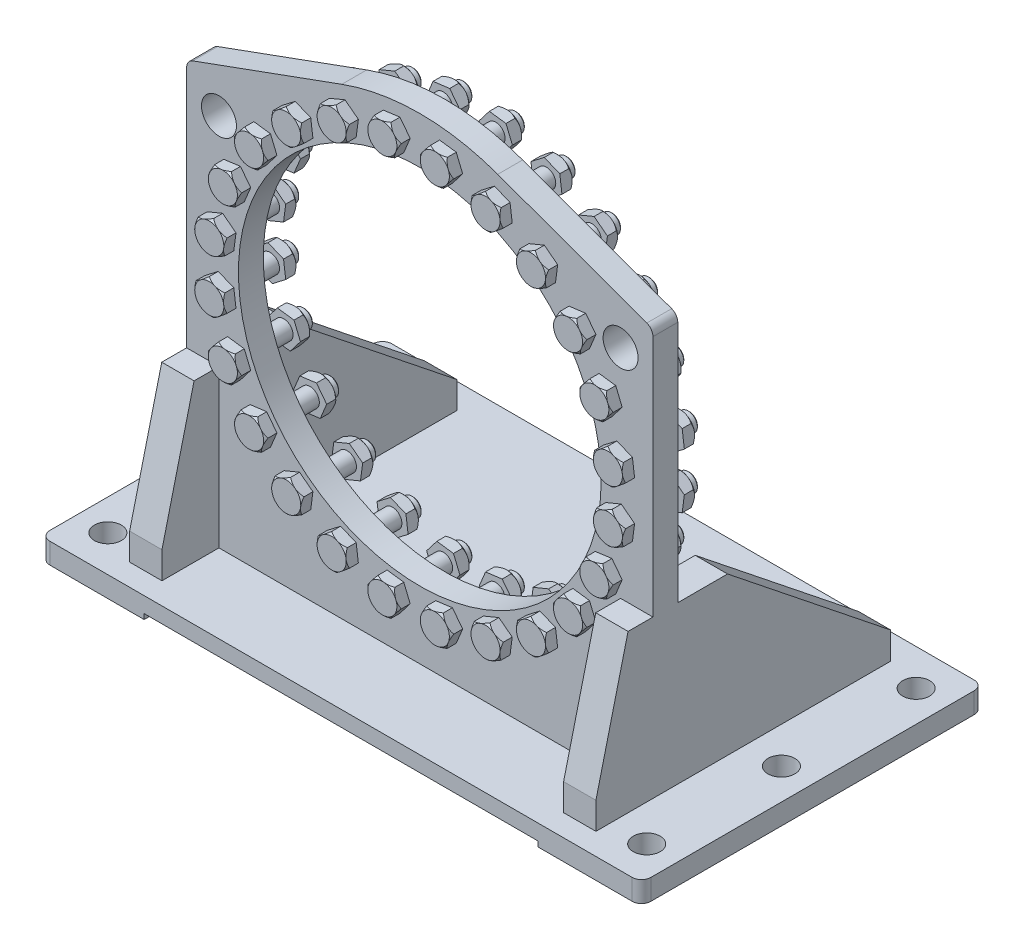
SolidWorks part; units mm, degrees
ref_plane "前视基准面" through (0, 0, 0) normal (0, 0, 1) x (1, 0, 0)
ref_plane "上视基准面" through (0, 0, 0) normal (0, 1, 0) x (1, 0, 0)
ref_plane "右视基准面" through (0, 0, 0) normal (1, 0, 0) x (0, 0, -1)
sketch "草图1" plane through (0, 0, 0) normal (1, 0, 0) x (0, 0, -1)
  line L1 (-305, 0) -> (24, 0) construction
  line L2 (0, 214) -> (24, 214)
  line L3 (24, 214) -> (24, 0)
  line L5 (0, 214) -> (0, 175)
  line L6 (0, 175) -> (-24, 175)
  line L10 (0, 194) -> (24, 194) construction
  line L32 (-24, 220) -> (-24, 175)
  line L34 (-48, -88.4) -> (48, -88.4)
  line L35 (48, -88.4) -> (205.5, -214)
  line L51 (205.5, -214) -> (205.5, -240)
  line L55 (205.5, -240) -> (-79, -240)
  line L56 (-79, -240) -> (-79, -214)
  line L57 (-79, -214) -> (-48, -88.4)
  line L58 (0, 175) -> (0, -260) construction
  line L59 (230, -260) -> (-100, -260)
  line L60 (455, -260) -> (325, -260) construction
  line L61 (325, -260) -> (195, -260) construction
  line L62 (24, 194) -> (34.8, 194) construction
  line L63 (195, -260) -> (65, -260) construction
  line L64 (65, -260) -> (-65, -260) construction
  line L65 (-24, 194) -> (-34.8, 194) construction
  line L66 (-24, 220) -> (0, 220)
  point P4 (24, 194)
  point P15 (0, 203)
  point P30 (43.8, 194)
  point P47 (-95, 0)
  point P48 (0, -88.4)
  point P52 (29.4, 194)
  point P53 (452, -260)
  dimension "D1" = 10.8
  dimension "G2" = 95
  dimension "C" = 24
  dimension "da" = 428
  dimension "d4" = 350
  dimension "k" = 388
  dimension "D2" = 21
  dimension "D3" = 24.5
  dimension "s" = 18
  dimension "D5" = 26
  dimension "D7" = 96
  dimension "D8" = 19.8
  dimension "n" = 24
  dimension "(c)" = 20
  dimension "(h)" = 260
  dimension "b" = 330
  dimension "m3" = 130
  dimension "(n)" = 35
  dimension "l2" = 210
  dimension "m4" = 240
  dimension "D6" = 171.6
  dimension "s(n)" = 3
  dimension "H" = 480
sketch "草图2" plane through (0, 0, 0) normal (0, 0, 1) x (1, 0, 0)
  line L0 (-190, -255) -> (190, -255)
  line L1 (190, -255) -> (190, -260)
  line L2 (290, -260) -> (-290, -260)
  line L3 (0, -260) -> (0, 0) construction
  line L5 (75.2444, 206.7324) -> (225, 152.2258)
  line L6 (225, 152.2258) -> (225, -260)
  line L7 (225, 121.0258) -> (193.8, 121.0258)
  line L8 (193.8, 121.0258) -> (193.8, 152.2258)
  line L9 (-260, -260) -> (-260, -240) construction
  line L10 (-260, -240) -> (225, -240)
  line L11 (193.8, -240) -> (193.8, -120)
  line L12 (193.8, -120) -> (225, -120)
  circle A0 centre (0, 0) radius 220
  circle A1 centre (193.8, 121.0258) radius 16.9
  circle A2 centre (0, 0) radius 175
  point P7 (0, -255)
  point P12 (0, 220)
  point P25 (-247, -260)
  dimension "D4" = 33.8
  dimension "D1" = 5
  dimension "e" = 380
  dimension "D2" = 70
  dimension "a" = 580
  dimension "d" = 450
  dimension "D3" = 120
  dimension "m1" = 520
  dimension "(s)" = 26
  dimension "D5" = 31.2
sketch "草图4" plane through (0, 0, 0) normal (0, 0, 1) x (1, 0, 0)
  line L0 (75.2444, 206.7324) -> (225, 152.2258) construction
  line L1 (225, 152.2258) -> (225, -260) construction
  line L2 (-260, -240) -> (225, -240) construction
  line L3 (75.2444, 206.7324) -> (225, 152.2258)
  line L4 (225, 152.2258) -> (225, -240)
  line L5 (-225, -240) -> (225, -240)
  line L6 (0, 214) -> (0, -240) construction
  line L7 (-225, 152.2258) -> (-225, -240)
  line L8 (-75.2444, 206.7324) -> (-225, 152.2258)
  circle A0 centre (0, 0) radius 220 construction
  circle A1 centre (193.8, 121.0258) radius 16.9 construction
  arc A2 (75.2444, 206.7324) -> (-75.2444, 206.7324) centre (0, 0) ccw
  circle A3 centre (193.8, 121.0258) radius 16.9
  circle A4 centre (-193.8, 121.0258) radius 16.9
  circle A5 centre (0, 0) radius 175 construction
  circle A6 centre (0, 0) radius 175
extrude "凸台-拉伸1" add sketch "草图4" along normal up to vertex (24 mm away) up to point (0, 220, 24)
sketch "草图6" plane through (0, 0, 0) normal (0, 0, -1) x (-1, 0, 0)
  line L0 (-26.4968, 201.2633) -> (-24.1473, 183.4173) construction
  line L1 (0, 175) -> (0, -260) construction
  circle A0 centre (0, 0) radius 194 construction
  circle A1 centre (-25.3221, 192.3403) radius 9
  circle A2 centre (0, 194) radius 9 construction
  dimension "D1" = 7.5
extrude "凸台-拉伸2" add sketch "草图6" along normal up to vertex (43.8 mm away) up to point (0, 194, -43.8)
chamfer "倒角1" distance 1.26 angle 45 1 edges at (16.3221, 192.3403, -43.8)
sketch "草图7" plane through (0, 0, 0) normal (0, 0, 1) x (1, 0, 0)
  line L0 (26.4968, 201.2633) -> (24.1473, 183.4173) construction
  line L1 (9.2488, 194.4564) -> (15.4528, 179.4785)
  line L2 (15.4528, 179.4785) -> (31.5261, 177.3624)
  line L3 (31.5261, 177.3624) -> (41.3954, 190.2242)
  line L4 (41.3954, 190.2242) -> (35.1913, 205.2021)
  line L5 (35.1913, 205.2021) -> (19.118, 207.3182)
  line L6 (19.118, 207.3182) -> (9.2488, 194.4564)
  circle A0 centre (25.3221, 192.3403) radius 14.04 construction
  dimension "D1" = 28.08
extrude "凸台-拉伸3" add sketch "草图7" against normal up to vertex (34.8 mm away) from vertex up to point (0, 194, -34.8) starting at point (0, 194, -24)
sketch "草图8" plane through (0, 0, -34.8) normal (0, 0, -1) x (-1, 0, 0)
  circle A0 centre (-25.3221, 192.3403) radius 14.04 construction
  circle A1 centre (-25.3221, 192.3403) radius 14.04
  circle A2 centre (-25.3221, 192.3403) radius 19.44
  dimension "D1" = 5.4
extrude "切除-拉伸1" cut sketch "草图8" against normal up to vertex (5.4 mm away) draft 45 up to point (0, 194, -29.4)
mirror "镜向2" about plane through (0, 0, 0) normal (0, 0, 1) of "切除-拉伸1", "凸台-拉伸3"
pattern_circular "阵列(圆周)1" count 24 over 360 about axis through (0, 0, 24) along (0, 0, -1) of "凸台-拉伸2", "倒角1", "凸台-拉伸3", "切除-拉伸1", "镜向2"
sketch "草图9" plane through (225, 0, 0) normal (-1, 0, 0) x (0, 0, 1)
  line L0 (-48, -88.4) -> (-205.5, -214) construction
  line L1 (48, -88.4) -> (-48, -88.4) construction
  line L2 (79, -214) -> (48, -88.4) construction
  line L3 (79, -240) -> (79, -214) construction
  line L12 (-205.5, -240) -> (79, -240) construction
  line L13 (-205.5, -214) -> (-205.5, -240) construction
  line L14 (-48, -88.4) -> (-205.5, -214)
  line L15 (48, -88.4) -> (-48, -88.4)
  line L16 (79, -214) -> (48, -88.4)
  line L17 (79, -240) -> (79, -214)
  line L18 (-205.5, -240) -> (79, -240)
  line L19 (-205.5, -214) -> (-205.5, -240)
extrude "凸台-拉伸4" add sketch "草图9" along normal up to vertex (31.2 mm away) up to point (193.8, -120, 0)
sketch "草图10" plane through (0, -240, 0) normal (0, -1, 0) x (1, 0, 0)
  line L1 (290, -230) -> (0, -230)
  line L2 (290, -230) -> (290, 100)
  line L3 (290, 100) -> (0, 100)
  line L4 (0, -230) -> (0, 100)
extrude "凸台-拉伸5" add sketch "草图10" along normal up to vertex (20 mm away) up to point (0, -260, -230)
sketch "草图11" plane through (0, -240, 0) normal (0, 1, 0) x (1, 0, 0)
  line L1 (0, 0) -> (0, -140.5) construction
  line L2 (0, -305) -> (0, 24) construction
  circle A0 centre (260, -65) radius 13
  circle A1 centre (-260, -65) radius 13 construction
  point P2 (-260, -65)
  point P8 (-247, -65)
extrude "切除-拉伸2" cut sketch "草图11" against normal up to vertex (20 mm away) up to point (290, -260, 0)
pattern_linear "阵列(线性)1" count 3 spacing 130 along (0, 0, -1) of "切除-拉伸2"
mirror "镜向3" about plane through (0, 0, 0) normal (1, 0, 0) of "阵列(线性)1", "切除-拉伸2", "凸台-拉伸4", "凸台-拉伸5"
fillet "圆角1" radius 9 6 edges at (225, 152.2258, 12) (-225, 152.2258, 12) (290, -250, -230) (290, -250, 100) (-290, -250, -230) (-290, -250, 100)
sketch "草图12" plane through (0, 0, 0) normal (0, 0, 1) x (1, 0, 0)
  line L0 (-190, -255) -> (-190, -260)
  line L1 (-190, -260) -> (190, -260)
  line L2 (190, -260) -> (190, -255)
  line L3 (190, -255) -> (-190, -255)
extrude "切除-拉伸3" cut sketch "草图12" against normal through all and the other way through all
equation "\"D2@草图1\" = \"(n)@草图1\"*0.6"
equation "\"D3@草图1\" = \"(n)@草图1\"*0.7"
equation "\"D5@草图1\" = \"(h)@草图1\"*0.1"
equation "\"D6@草图1\" = \"(h)@草图1\"*0.66"
equation "\"D7@草图1\" = \"C@草图1\"*4"
equation "\"D4@草图2\" = \"(s)@草图2\"*1.3"
equation "\"D5@草图2\" = \"(s)@草图2\"*1.2"
equation "\"D1@草图1\" = \"s@草图1\"*0.6"
equation "\"D8@草图1\" = \"s@草图1\"*1.1"
equation "\"D1@草图6\" = 180/\"n@草图1\""
equation "\"D1@倒角1\" = \"s@草图1\"*0.07"
equation "\"D1@草图7\" = \"s@草图1\"*1.56"
equation "\"D1@草图8\" = \"s@草图1\"*0.3"
equation "\"D1@阵列(圆周)1\" = \"n@草图1\""
equation "\"D1@阵列(线性)1\" = \"s(n)@草图1\""
equation "\"D3@阵列(线性)1\" = \"m3@草图1\""
equation "\"D1@圆角1\" = \"s@草图1\"/2"
equation "\"D3@草图2\" = \"H@草图1\" * 0.25"
